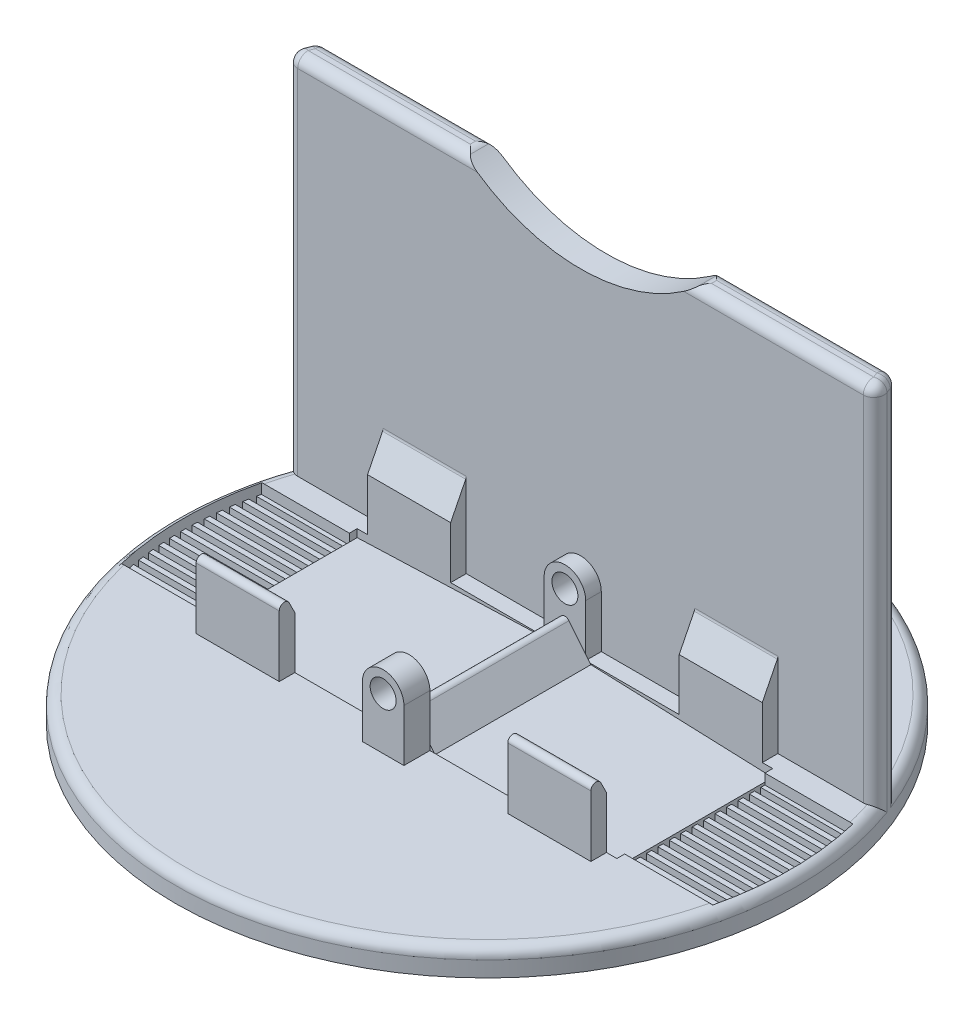
SolidWorks part; units mm, degrees
ref_plane "Front Plane" through (0, 0, 0) normal (0, 0, 1) x (1, 0, 0)
ref_plane "Top Plane" through (0, 0, 0) normal (0, 1, 0) x (1, 0, 0)
ref_plane "Right Plane" through (0, 0, 0) normal (1, 0, 0) x (0, 0, -1)
sketch "Sketch1" plane through (0, 0, 0) normal (0, 1, 0) x (1, 0, 0)
  circle A0 centre (0, 0) radius 76.2
  dimension "D1" = 152.4
extrude "Boss-Extrude1" add sketch "Sketch1" along normal blind 6.35
sketch "Sketch2" plane through (0, 6.35, 0) normal (0, 1, 0) x (1, 0, 0)
  line L0 (-76.2, 0) -> (76.2, 0) construction
  line L1 (0, 76.2) -> (0, -76.2) construction
  line L2 (-73.7803, 19.05) -> (73.7803, 19.05) construction
  line L3 (-50.8, 19.05) -> (-50.8, -19.05) construction
  line L4 (50.8, 19.05) -> (50.8, -19.05) construction
  line L5 (-73.7803, -19.05) -> (73.7803, -19.05) construction
  line L6 (-72.2897, -17.145) -> (72.2897, -17.145)
  line L7 (-72.2897, 17.145) -> (72.2897, 17.145)
  line L8 (-50.8, -17.145) -> (-50.8, 17.145)
  line L9 (50.8, 17.145) -> (50.8, -17.145)
  circle A0 centre (0, 0) radius 76.2 construction
  arc A1 (-73.7803, 19.05) -> (-73.7803, -19.05) centre (0, 0) ccw construction
  arc A2 (73.7803, -19.05) -> (73.7803, 19.05) centre (0, 0) ccw construction
  arc A3 (-72.2897, 17.145) -> (-72.2897, -17.145) centre (0, 0) ccw
  arc A4 (72.2897, -17.145) -> (72.2897, 17.145) centre (0, 0) ccw
  point P14 (50.8, 0)
  point P17 (-50.8, 0)
  dimension "D1" = 19.05
  dimension "D2" = 50.8
  dimension "D3" = 1.905
extrude "Cut-Extrude1" cut sketch "Sketch2" against normal blind 2.54 contours L7 A3 L6 L3 | L6 A4 L7 L9
sketch "Sketch3" plane through (0, 6.35, 0) normal (0, 1, 0) x (1, 0, 0)
  line L0 (0, 76.2) -> (0, -76.2) construction
  line L1 (-5.08, 25.4) -> (5.08, 25.4)
  line L2 (-5.08, 25.4) -> (-5.08, 19.05)
  line L3 (-5.08, 19.05) -> (5.08, 19.05)
  line L4 (5.08, 25.4) -> (5.08, 19.05)
  line L5 (-5.08, 25.4) -> (5.08, 19.05) construction
  line L6 (-5.08, 19.05) -> (5.08, 25.4) construction
  line L7 (-76.2, 0) -> (76.2, 0) construction
  line L9 (-73.7803, 19.05) -> (73.7803, 19.05) construction
  line L10 (-5.08, -19.05) -> (5.08, -19.05)
  line L11 (5.08, -25.4) -> (5.08, -19.05)
  line L12 (-5.08, -25.4) -> (5.08, -25.4)
  line L13 (-5.08, -25.4) -> (-5.08, -19.05)
  line L14 (-48.26, -19.05) -> (-27.94, -19.05)
  line L15 (-48.26, 22.86) -> (-27.94, 22.86)
  line L16 (-48.26, 22.86) -> (-48.26, 19.05)
  line L17 (-48.26, 19.05) -> (-27.94, 19.05)
  line L18 (-27.94, 22.86) -> (-27.94, 19.05)
  line L19 (-48.26, 22.86) -> (-27.94, 19.05) construction
  line L20 (-48.26, 19.05) -> (-27.94, 22.86) construction
  line L21 (-27.94, -22.86) -> (-27.94, -19.05)
  line L22 (-48.26, -22.86) -> (-27.94, -22.86)
  line L23 (-48.26, -22.86) -> (-48.26, -19.05)
  line L24 (0, 76.2) -> (0, -76.2) construction
  line L25 (48.26, -22.86) -> (48.26, -19.05)
  line L26 (48.26, -22.86) -> (27.94, -22.86)
  line L27 (27.94, -22.86) -> (27.94, -19.05)
  line L28 (48.26, -19.05) -> (27.94, -19.05)
  line L29 (48.26, 19.05) -> (27.94, 19.05)
  line L30 (27.94, 22.86) -> (27.94, 19.05)
  line L31 (48.26, 22.86) -> (27.94, 22.86)
  line L32 (48.26, 22.86) -> (48.26, 19.05)
  point P0 (0, 22.225)
  point P17 (-38.1, 20.955)
  dimension "D1" = 6.35
  dimension "D2" = 10.16
  dimension "D3" = 3.81
  dimension "D4" = 20.32
  dimension "D5" = 38.1
extrude "Boss-Extrude2" add sketch "Sketch3" along normal blind 12.7
sketch "Sketch4" plane through (0, 0, -25.4) normal (0, 0, -1) x (-1, 0, 0)
  line L0 (-5.08, 19.05) -> (5.08, 19.05) construction
  line L5 (-5.08, 6.35) -> (5.08, 6.35)
  line L6 (5.08, 6.35) -> (5.08, 19.05)
  line L7 (5.08, 19.05) -> (-5.08, 19.05)
  line L8 (-5.08, 19.05) -> (-5.08, 6.35)
  line L9 (-5.08, 6.35) -> (5.08, 6.35)
  line L10 (5.08, 6.35) -> (5.08, 19.05)
  line L12 (-5.08, 19.05) -> (-5.08, 6.35)
  arc A0 (-5.08, 19.05) -> (5.08, 19.05) centre (0, 19.05) cw
  dimension "D1" = 0
extrude "Boss-Extrude3" add sketch "Sketch4" against normal up to surface (6.35 mm away) up to face at (0, 12.7, -19.05)
sketch "Sketch5" plane through (0, 0, 25.4) normal (0, 0, 1) x (1, 0, 0)
  line L1 (-5.08, 19.05) -> (5.08, 19.05) construction
  line L2 (-5.08, 19.05) -> (5.08, 19.05)
  arc A0 (-5.08, 19.05) -> (5.08, 19.05) centre (0, 19.05) cw
extrude "Boss-Extrude4" add sketch "Sketch5" against normal up to surface (6.35 mm away) up to face at (0, 12.7, 19.05)
sketch "Sketch7" plane through (0, 6.35, 0) normal (0, 1, 0) x (1, 0, 0)
  line L0 (-72.6902, 22.86) -> (72.6902, 22.86)
  line L2 (-70.3791, 29.21) -> (70.3791, 29.21)
  line L4 (48.26, 22.86) -> (27.94, 22.86) construction
  circle A0 centre (0, 0) radius 76.2 construction
  arc A1 (-70.3791, 29.21) -> (-72.6902, 22.86) centre (0, 0) ccw
  arc A2 (72.6902, 22.86) -> (70.3791, 29.21) centre (0, 0) ccw
  dimension "D2" = 6.35
sketch "Sketch10" plane through (0, 3.81, 0) normal (0, 1, 0) x (1, 0, 0)
  line L0 (-72.5231, 16.129) -> (-50.8, 16.129)
  line L1 (-50.8, -17.145) -> (-50.8, 17.145) construction
  line L2 (-50.8, 16.129) -> (-50.8, 14.605)
  line L3 (-50.8, 14.605) -> (-72.8453, 14.605)
  line L4 (-73.3502, 11.811) -> (-50.8, 11.811)
  line L5 (-50.8, 11.811) -> (-50.8, 13.335)
  line L6 (-50.8, 13.335) -> (-73.0885, 13.335)
  line L7 (-73.5434, 10.541) -> (-50.8, 10.541)
  line L8 (-50.8, 10.541) -> (-50.8, 9.017)
  line L9 (-50.8, 9.017) -> (-73.7458, 9.017)
  line L10 (-74.2158, 3.429) -> (-50.8, 3.429)
  line L11 (-50.8, 3.429) -> (-50.8, 4.953)
  line L12 (-50.8, 4.953) -> (-74.1297, 4.953)
  line L13 (-50.8, 6.223) -> (-74.0339, 6.223)
  line L14 (-50.8, 6.223) -> (-50.8, 7.747)
  line L15 (-50.8, 7.747) -> (-73.89, 7.747)
  line L16 (-74.2636, 2.159) -> (-50.8, 2.159)
  line L17 (-50.8, 2.159) -> (-50.8, 0.635)
  line L18 (-50.8, 0.635) -> (-74.2923, 0.635)
  line L19 (-74.2923, -0.635) -> (-50.8, -0.635)
  line L20 (-50.8, -0.635) -> (-50.8, -2.159)
  line L21 (-50.8, -2.159) -> (-74.2636, -2.159)
  line L22 (-72.2897, 17.145) -> (72.2897, 17.145) construction
  line L23 (-74.2158, -3.429) -> (-50.8, -3.429)
  line L24 (-50.8, -17.145) -> (-50.8, 17.145) construction
  line L25 (0, 76.2) -> (0, -76.2) construction
  line L47 (-50.8, -3.429) -> (-50.8, -4.953)
  line L48 (-50.8, -4.953) -> (-74.1297, -4.953)
  line L49 (-50.8, -6.223) -> (-74.0339, -6.223)
  line L50 (-50.8, -6.223) -> (-50.8, -7.747)
  line L51 (-50.8, -7.747) -> (-73.89, -7.747)
  line L52 (-73.7458, -9.017) -> (-50.8, -9.017)
  line L53 (-50.8, -9.017) -> (-50.8, -10.541)
  line L54 (-50.8, -10.541) -> (-73.5434, -10.541)
  line L55 (-50.8, -11.811) -> (-73.3502, -11.811)
  line L56 (-50.8, -11.811) -> (-50.8, -13.335)
  line L57 (-50.8, -13.335) -> (-73.0885, -13.335)
  line L58 (-50.8, -14.605) -> (-72.8453, -14.605)
  line L59 (-50.8, -14.605) -> (-50.8, -16.129)
  line L60 (-50.8, -16.129) -> (-72.5231, -16.129)
  line L61 (50.8, 16.129) -> (72.5231, 16.129)
  line L62 (50.8, 17.145) -> (50.8, -17.145) construction
  line L65 (50.8, 16.129) -> (50.8, 14.605)
  line L66 (50.8, 14.605) -> (72.8453, 14.605)
  line L69 (50.8, 13.335) -> (73.0885, 13.335)
  line L72 (50.8, 13.335) -> (50.8, 11.811)
  line L73 (50.8, 11.811) -> (73.3502, 11.811)
  line L76 (73.5434, 10.541) -> (50.8, 10.541)
  line L77 (50.8, 10.541) -> (50.8, 9.017)
  line L78 (50.8, 9.017) -> (73.7458, 9.017)
  line L79 (50.8, 7.747) -> (73.89, 7.747)
  line L80 (50.8, 7.747) -> (50.8, 6.223)
  line L81 (50.8, 6.223) -> (74.0339, 6.223)
  line L82 (50.8, 4.953) -> (74.1297, 4.953)
  line L83 (50.8, 4.953) -> (50.8, 3.429)
  line L84 (50.8, 3.429) -> (74.2158, 3.429)
  line L85 (50.8, 2.159) -> (74.2636, 2.159)
  line L86 (50.8, 2.159) -> (50.8, 0.635)
  line L87 (50.8, 0.635) -> (74.2923, 0.635)
  line L88 (50.8, 17.145) -> (72.2897, 17.145) construction
  line L89 (50.8, -2.159) -> (50.8, -0.635)
  line L90 (50.8, -0.635) -> (74.2923, -0.635)
  line L91 (50.8, -2.159) -> (74.2636, -2.159)
  line L92 (50.8, -3.429) -> (50.8, -4.953)
  line L93 (50.8, -4.953) -> (74.1297, -4.953)
  line L94 (50.8, -3.429) -> (74.2158, -3.429)
  line L95 (74.0339, -6.223) -> (50.8, -6.223)
  line L96 (50.8, -6.223) -> (50.8, -7.747)
  line L97 (50.8, -7.747) -> (73.89, -7.747)
  line L98 (73.7458, -9.017) -> (50.8, -9.017)
  line L99 (50.8, -9.017) -> (50.8, -10.541)
  line L100 (50.8, -10.541) -> (73.5434, -10.541)
  line L101 (50.8, -11.811) -> (73.3502, -11.811)
  line L102 (50.8, -11.811) -> (50.8, -13.335)
  line L103 (50.8, -13.335) -> (73.0885, -13.335)
  line L104 (72.8453, -14.605) -> (50.8, -14.605)
  line L105 (50.8, -14.605) -> (50.8, -16.129)
  line L106 (50.8, -16.129) -> (72.5231, -16.129)
  arc A0 (-72.2897, 17.145) -> (-72.2897, -17.145) centre (0, 0) ccw construction
  arc A1 (-72.5231, 16.129) -> (-72.8453, 14.605) centre (0, 0) ccw
  arc A2 (-73.0885, 13.335) -> (-73.3502, 11.811) centre (0, 0) ccw
  arc A3 (-73.5434, 10.541) -> (-73.7458, 9.017) centre (0, 0) ccw
  arc A4 (-73.89, 7.747) -> (-74.0339, 6.223) centre (0, 0) ccw
  arc A5 (-74.1297, 4.953) -> (-74.2158, 3.429) centre (0, 0) ccw
  arc A6 (-74.2636, 2.159) -> (-74.2923, 0.635) centre (0, 0) ccw
  arc A7 (-74.2923, -0.635) -> (-74.2636, -2.159) centre (0, 0) ccw
  arc A15 (-72.2897, 17.145) -> (-72.2897, -17.145) centre (0, 0) ccw construction
  arc A16 (-72.5231, 16.129) -> (-72.8453, 14.605) centre (0, 0) ccw
  arc A17 (-73.0885, 13.335) -> (-73.3502, 11.811) centre (0, 0) ccw
  arc A18 (-73.5434, 10.541) -> (-73.7458, 9.017) centre (0, 0) ccw
  arc A19 (-73.89, 7.747) -> (-74.0339, 6.223) centre (0, 0) ccw
  arc A20 (-74.1297, 4.953) -> (-74.2158, 3.429) centre (0, 0) ccw
  arc A21 (-74.2636, 2.159) -> (-74.2923, 0.635) centre (0, 0) ccw
  arc A22 (-74.2923, -0.635) -> (-74.2636, -2.159) centre (0, 0) ccw
  arc A23 (-74.2158, -3.429) -> (-74.1297, -4.953) centre (0, 0) ccw
  arc A24 (-74.0339, -6.223) -> (-73.89, -7.747) centre (0, 0) ccw
  arc A25 (-73.7458, -9.017) -> (-73.5434, -10.541) centre (0, 0) ccw
  arc A26 (-73.3502, -11.811) -> (-73.0885, -13.335) centre (0, 0) ccw
  arc A27 (-72.8453, -14.605) -> (-72.5231, -16.129) centre (0, 0) ccw
  arc A28 (72.2897, -17.145) -> (72.2897, 17.145) centre (0, 0) ccw construction
  arc A29 (72.5231, -16.129) -> (72.8453, -14.605) centre (0, 0) ccw
  arc A30 (72.8453, 14.605) -> (72.5231, 16.129) centre (0, 0) ccw
  arc A31 (73.3502, 11.811) -> (73.0885, 13.335) centre (0, 0) ccw
  arc A32 (73.7458, 9.017) -> (73.5434, 10.541) centre (0, 0) ccw
  arc A33 (74.0339, 6.223) -> (73.89, 7.747) centre (0, 0) ccw
  arc A34 (74.2158, 3.429) -> (74.1297, 4.953) centre (0, 0) ccw
  arc A35 (74.2923, 0.635) -> (74.2636, 2.159) centre (0, 0) ccw
  arc A36 (74.2636, -2.159) -> (74.2923, -0.635) centre (0, 0) ccw
  arc A37 (74.1297, -4.953) -> (74.2158, -3.429) centre (0, 0) ccw
  arc A38 (73.89, -7.747) -> (74.0339, -6.223) centre (0, 0) ccw
  arc A39 (73.5434, -10.541) -> (73.7458, -9.017) centre (0, 0) ccw
  arc A40 (73.0885, -13.335) -> (73.3502, -11.811) centre (0, 0) ccw
  dimension "D1" = 1.524
  dimension "D2" = 1.27
  dimension "D3" = 1.27
  dimension "D4" = 1.27
  dimension "D5" = 1.27
  dimension "D6" = 1.27
  dimension "D7" = 1.27
  dimension "D8" = 1.016
  dimension "D9" = 1.27
  dimension "D10" = 1.27
  dimension "D11" = 1.27
  dimension "D12" = 1.27
  dimension "D13" = 1.27
  dimension "D14" = 1.524
  dimension "D15" = 1.016
  dimension "D16" = 1.27
  dimension "D17" = 1.27
  dimension "D18" = 1.27
  dimension "D19" = 1.27
  dimension "D20" = 1.27
  dimension "D21" = 1.27
  dimension "D22" = 1.27
  dimension "D23" = 1.27
  dimension "D24" = 1.27
  dimension "D25" = 1.27
extrude "Cut-Extrude3" cut sketch "Sketch10" along normal up to surface (6.35 mm away) from surface contours L0 L2 L3 A1 | L6 A2 L4 L5 | L7 L8 L9 A3 | L15 A4 L13 L14 | L12 A5 L10 L11 | L16 L17 L18 A6 | L19 L20 L21 A7 | L23 L47 L48 A23 | L49 A24 L51 L50 | L52 L53 L54 A25 | L55 A26 L57 L56 | L58 A27 L60 L59 | L61 A30 L66 L65 | L69 A31 L73 L72 | L76 L77 L78 A32 | L79 A33 L81 L80 | L82 A34 L84 L83 | L85 A35 L87 L86 | L90 A36 L91 L89 | L94 A37 L93 L92 | L95 L96 L97 A38 | L98 L99 L100 A39 | L101 A40 L103 L102 | A29 L104 L105 L106
extrude "Boss-Extrude6" add sketch "Sketch7" along normal blind 88.9
sketch "Sketch11" plane through (0, 0, 25.4) normal (0, 0, 1) x (1, 0, 0)
  line L0 (-5.08, 19.05) -> (5.08, 19.05) construction
  circle A0 centre (0, 19.05) radius 3.175
  dimension "D1" = 6.35
extrude "Cut-Extrude5" cut sketch "Sketch11" against normal through all
sketch "Sketch13" plane through (-48.26, 0, 0) normal (-1, 0, 0) x (0, 0, 1)
  line L0 (19.05, 19.05) -> (22.86, 26.67)
  line L1 (22.86, 19.05) -> (22.86, 26.67)
  line L2 (0, 0) -> (0, 39.3046) construction
  line L3 (19.05, 19.05) -> (22.86, 19.05)
  line L4 (-19.05, 19.05) -> (-22.86, 26.67)
  line L5 (-22.86, 19.05) -> (-22.86, 26.67)
  line L6 (-19.05, 19.05) -> (-22.86, 19.05)
  dimension "D1" = 7.62
extrude "Boss-Extrude7" add sketch "Sketch13" against normal up to surface (20.32 mm away) up to face at (-27.94, 12.7, -20.955)
sketch "Sketch14" plane through (48.26, 0, 0) normal (1, 0, 0) x (0, 0, -1)
  line L16 (19.05, 6.35) -> (22.86, 6.35) construction
  line L17 (22.86, 6.35) -> (22.86, 26.67) construction
  line L18 (22.86, 26.67) -> (19.05, 19.05) construction
  line L19 (19.05, 19.05) -> (19.05, 6.35) construction
  line L20 (-22.86, 6.35) -> (-19.05, 6.35) construction
  line L21 (-19.05, 6.35) -> (-19.05, 19.05) construction
  line L22 (-19.05, 19.05) -> (-22.86, 26.67) construction
  line L23 (-22.86, 26.67) -> (-22.86, 6.35) construction
  line L24 (19.05, 6.35) -> (22.86, 6.35)
  line L25 (22.86, 6.35) -> (22.86, 26.67)
  line L26 (22.86, 26.67) -> (19.05, 19.05)
  line L27 (19.05, 19.05) -> (19.05, 6.35)
  line L28 (-22.86, 6.35) -> (-19.05, 6.35)
  line L29 (-19.05, 6.35) -> (-19.05, 19.05)
  line L30 (-19.05, 19.05) -> (-22.86, 26.67)
  line L31 (-22.86, 26.67) -> (-22.86, 6.35)
extrude "Boss-Extrude8" add sketch "Sketch14" against normal up to surface (20.32 mm away) up to face at (27.94, 12.7, -20.955)
sketch "Sketch15" plane through (0, 0, 0) normal (0, 0, 1) x (1, 0, 0)
  line L0 (0, 6.35) -> (50.8, 4.445)
  line L1 (-72.2897, 6.35) -> (72.2897, 6.35) construction
  line L2 (50.8, 4.445) -> (0, 0) construction
  line L3 (0, 0) -> (0, 6.35) construction
  line L4 (0, 6.35) -> (-50.8, 4.445)
  line L5 (-50.8, 4.445) -> (0, 0) construction
  line L6 (50.8, 3.81) -> (50.8, 6.35) construction
  line L7 (0, 6.35) -> (50.8, 6.35)
  line L8 (50.8, 6.35) -> (50.8, 4.445)
  line L9 (0, 6.35) -> (-50.8, 6.35)
  line L10 (-50.8, 6.35) -> (-50.8, 4.445)
  dimension "D1" = 4.445
extrude "Cut-Extrude6" cut sketch "Sketch15" against normal mid plane 38.1 contours L0 L8 L7 | L4 L10 L9
sketch "Sketch16" plane through (0, 0, -19.05) normal (0, 0, 1) x (1, 0, 0)
  line L0 (-6.35, 6.1119) -> (0, 13.97)
  line L1 (0, 6.35) -> (-50.8, 4.445) construction
  line L2 (0, 13.97) -> (0, 6.35) construction
  line L3 (0, 6.35) -> (50.8, 4.445) construction
  line L4 (0, 6.35) -> (-6.35, 6.1119)
  line L5 (6.35, 6.1119) -> (0, 13.97)
  line L6 (0, 6.35) -> (6.35, 6.1119)
  line L7 (0, 6.35) -> (-50.8, 4.445) construction
  dimension "D1" = 7.62
  dimension "D2" = 12.7
extrude "Boss-Extrude9" add sketch "Sketch16" along normal up to surface (38.1 mm away) up to face at (3.175, 19.05, 19.05)
sketch "Sketch17" plane through (0, 0, -22.86) normal (0, 0, 1) x (1, 0, 0)
  line L0 (-72.6902, 95.25) -> (72.6902, 95.25) construction
  line L1 (0, 0) -> (0, 95.25) construction
  line L2 (-76.2, 0) -> (76.2, 0) construction
  line L3 (-28.575, 95.25) -> (28.575, 95.25)
  arc A0 (-28.575, 95.25) -> (28.575, 95.25) centre (0, 129.2981) ccw
  point P9 (0, 84.8481)
  dimension "D2" = 44.45
  dimension "D1" = 57.15
extrude "Cut-Extrude7" cut sketch "Sketch17" against normal up to surface (6.35 mm away) up to face at (3.175, 19.05, -29.21)
fillet "Fillet1" radius 2.54 14 edges at (70.3791, 50.8, -29.21) (-70.3791, 50.8, -29.21) (-72.6902, 50.8, -22.86) (72.6902, 50.8, -22.86) (-49.477, 95.25, -29.21) (49.477, 95.25, -29.21) (50.6326, 95.25, -22.86) (-50.6326, 95.25, -22.86) (0, 6.35, -76.2) (0, 6.35, 76.2) (71.6051, 95.25, -26.0606) (-71.6051, 95.25, -26.0606) (-28.575, 95.25, -26.035) (28.575, 95.25, -26.035)
fillet "Fillet2" radius 1.27 1 edges at (0, 13.97, 0)
fillet "Fillet3" radius 1.27 4 edges at (-38.1, 26.67, -22.86) (38.1, 26.67, -22.86) (38.1, 26.67, 22.86) (-38.1, 26.67, 22.86)
